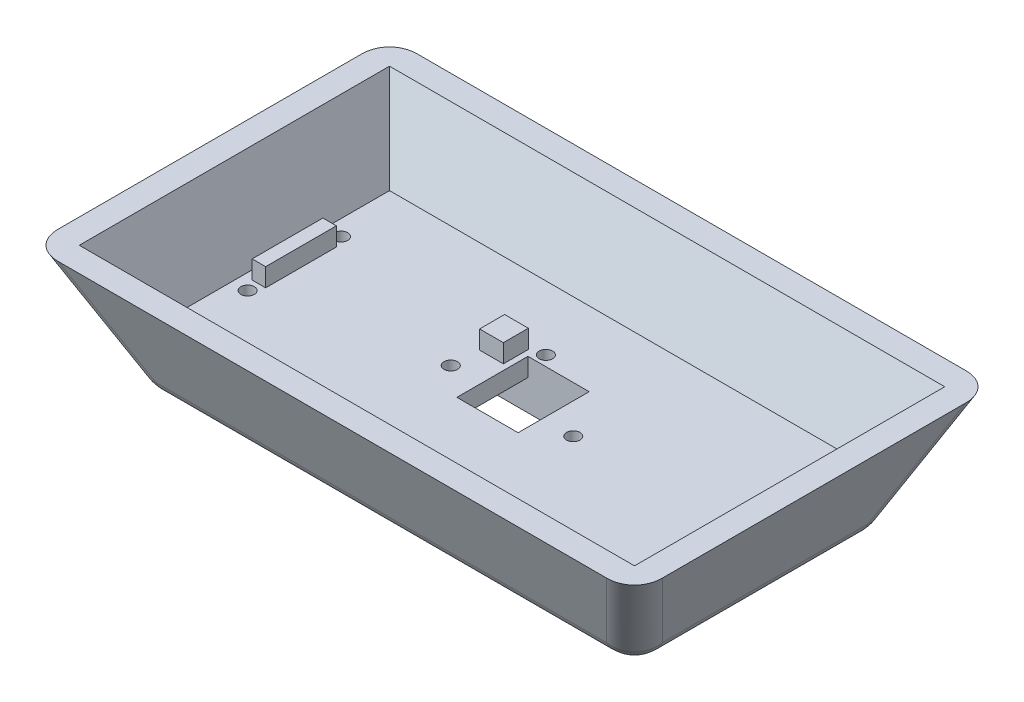
SolidWorks part; units mm, degrees
ref_plane "Front Plane" through (0, 0, 0) normal (0, 0, 1) x (1, 0, 0)
ref_plane "Top Plane" through (0, 0, 0) normal (0, 1, 0) x (1, 0, 0)
ref_plane "Right Plane" through (0, 0, 0) normal (1, 0, 0) x (0, 0, -1)
sketch "Sketch1" plane through (0, 0, 0) normal (0, 1, 0) x (1, 0, 0)
  line L1 (-40, 20) -> (40, 20)
  line L2 (-40, 20) -> (-40, -20)
  line L3 (-40, -20) -> (40, -20)
  line L4 (40, 20) -> (40, -20)
  line L5 (-40, 20) -> (40, -20) construction
  line L6 (-40, -20) -> (40, 20) construction
  point P0 (0, 0)
  dimension "D1" = 40
  dimension "D2" = 80
extrude "Boss-Extrude1" add sketch "Sketch1" along normal blind 20 draft 25 draft outward yes
sketch "Sketch2" plane through (0, 0, 0) normal (0, -1, 0) x (1, 0, 0)
  line L1 (-15.1, 7.6) -> (15.1, 7.6)
  line L2 (-15.1, 7.6) -> (-15.1, -7.6)
  line L3 (-15.1, -7.6) -> (15.1, -7.6)
  line L4 (15.1, 7.6) -> (15.1, -7.6)
  line L5 (-15.1, 7.6) -> (15.1, -7.6) construction
  line L6 (-15.1, -7.6) -> (15.1, 7.6) construction
  point P0 (0, 0)
  dimension "D1" = 15.2
  dimension "D2" = 30.2
extrude "Cut-Extrude1" cut sketch "Sketch2" against normal blind 5
sketch "Sketch3" plane through (0, 20, 0) normal (0, 1, 0) x (1, 0, 0)
  line L17 (-45.3262, 25.3262) -> (-45.3262, -25.3262)
  line L18 (-45.3262, -25.3262) -> (45.3262, -25.3262)
  line L19 (45.3262, -25.3262) -> (45.3262, 25.3262)
  line L20 (45.3262, 25.3262) -> (-45.3262, 25.3262)
  line L21 (-45.3262, 25.3262) -> (-45.3262, -25.3262)
  line L22 (-45.3262, -25.3262) -> (45.3262, -25.3262)
  line L23 (45.3262, -25.3262) -> (45.3262, 25.3262)
  line L24 (45.3262, 25.3262) -> (-45.3262, 25.3262)
  dimension "D2" = 4
extrude "Cut-Extrude3" cut sketch "Sketch3" against normal blind 12 draft 25
sketch "Sketch5" plane through (0, 5, 0) normal (0, -1, 0) x (1, 0, 0)
  line L0 (0, 0) -> (-10, 0) construction
  line L1 (0, 0) -> (10, 0) construction
  line L2 (-5, 0) -> (-5, 4) construction
  line L4 (-5, 4) -> (5, 4) construction
  line L5 (-15.1, -7.6) -> (15.1, -7.6) construction
  line L6 (5, 4) -> (-5, 4)
  line L7 (5, 4) -> (5, -7.6)
  line L8 (5, -7.6) -> (-5, -7.6)
  line L9 (-5, 4) -> (-5, -7.6)
  circle A0 centre (-10, 0) radius 1.1
  circle A1 centre (10, 0) radius 1.1
  dimension "D3" = 2.2
  dimension "D4" = 2.2
  dimension "D1" = 10
  dimension "D2" = 10
  dimension "D5" = 4
  dimension "D6" = 10
extrude "Cut-Extrude4" cut sketch "Sketch5" against normal up to next
sketch "Sketch6" plane through (0, 8, 0) normal (0, 1, 0) x (1, 0, 0)
  line L0 (-5, 1.8) -> (-39.7305, 1.8) construction
  line L1 (-5, -4) -> (-5, 7.6) construction
  line L2 (-39.7305, 19.7305) -> (-39.7305, -19.7305) construction
  line L3 (-39.7305, 1.8) -> (-39.7305, -8.7) construction
  line L4 (-39.7305, -8.7) -> (-1.7305, -8.7) construction
  line L5 (-39.7305, 1.8) -> (-39.7305, 12.3) construction
  line L6 (-39.7305, -8.7) -> (-39.7305, -5.98) construction
  line L7 (-39.7305, 12.3) -> (-1.7305, 12.3)
  line L8 (-39.7305, 12.3) -> (-39.7305, -8.7)
  line L9 (-39.7305, -8.7) -> (-1.7305, -8.7)
  line L10 (-1.7305, 12.3) -> (-1.7305, -8.7)
  line L11 (-39.7305, -5.98) -> (-37.1905, -5.98) construction
  line L12 (-39.7305, -8.7) -> (-39.7305, 9.27) construction
  line L13 (-39.7305, 9.27) -> (-37.1905, 9.27) construction
  line L14 (-39.7305, 9.27) -> (-3.7305, 9.27) construction
  circle A0 centre (-37.1905, -5.98) radius 1.1
  circle A1 centre (-37.1905, 9.27) radius 1.1
  circle A2 centre (-3.7305, 9.27) radius 1.1
  point P18 (0, 0)
  dimension "D1" = 2.2
  dimension "D2" = 2.2
  dimension "D3" = 2.2
extrude "Cut-Extrude5" cut sketch "Sketch6" against normal blind 4.75 contours A1 | A0 | A2
sketch "Sketch7" plane through (0, 8, 0) normal (0, 1, 0) x (1, 0, 0)
  line L1 (-38.2905, 9.27) -> (-38.2905, -5.98) construction
  line L2 (-36.0905, 9.27) -> (-36.0905, -5.98) construction
  line L3 (-37.1905, 8.17) -> (-37.1905, 7.42) construction
  line L4 (-37.1905, -4.88) -> (-37.1905, -4.13) construction
  line L6 (-38.2905, 7.42) -> (-36.0905, 7.42)
  line L7 (-38.2905, 7.42) -> (-38.2905, -4.13)
  line L8 (-38.2905, -4.13) -> (-36.0905, -4.13)
  line L9 (-36.0905, 7.42) -> (-36.0905, -4.13)
  line L10 (-9.8176, 8.6092) -> (-5.9359, 8.6092)
  line L11 (-9.8176, 8.6092) -> (-9.8176, 4.53)
  line L12 (-9.8176, 4.53) -> (-5.9359, 4.53)
  line L13 (-5.9359, 8.6092) -> (-5.9359, 4.53)
  circle A0 centre (-37.1905, 9.27) radius 1.1 construction
  circle A1 centre (-37.1905, 9.27) radius 1.1 construction
  circle A2 centre (-37.1905, -5.98) radius 1.1 construction
  circle A3 centre (-37.1905, -5.98) radius 1.1 construction
  dimension "D1" = 0.75
extrude "Boss-Extrude3" add sketch "Sketch7" along normal blind 3
fillet "Fillet1" radius 5 8 edges at (-40, 0, 0) (0, 0, 20) (40, 0, 0) (0, 0, -20) (-44.6631, 10, 24.6631) (44.6631, 10, 24.6631) (44.6631, 10, -24.6631) (-44.6631, 10, -24.6631)
